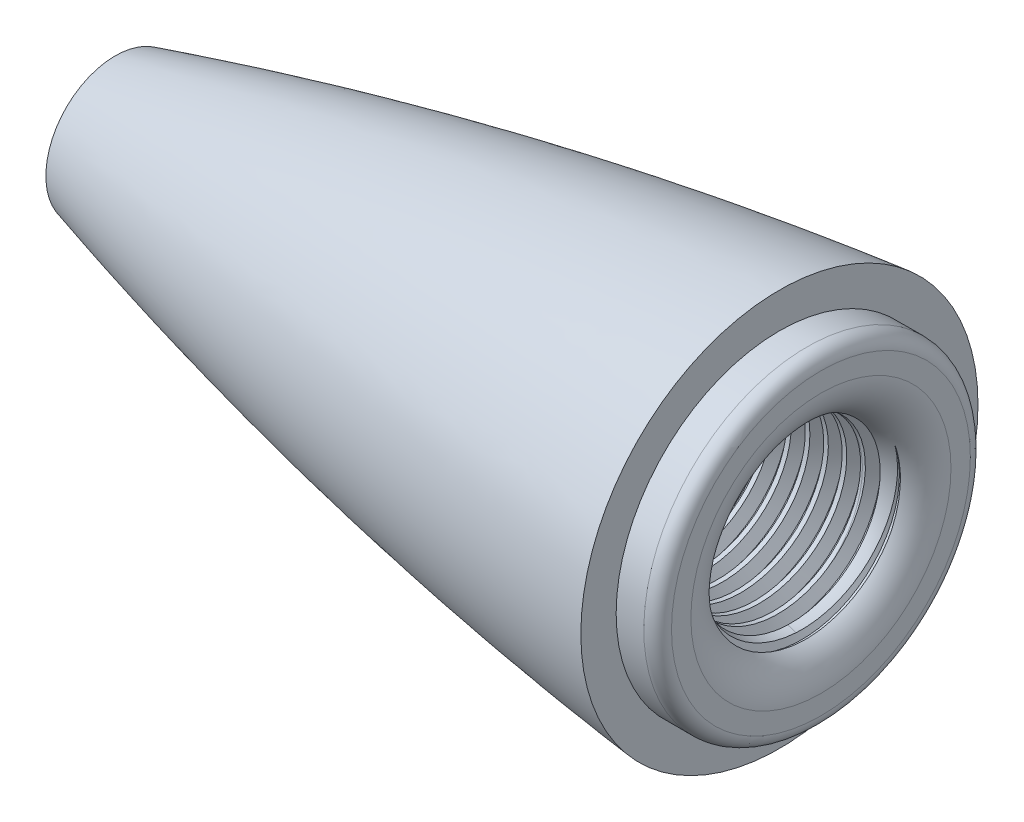
SolidWorks part; units mm, degrees
material "PVC Rigid"
ref_plane "Front Plane" through (0, 0, 0) normal (0, 0, 1) x (1, 0, 0)
ref_plane "Top Plane" through (0, 0, 0) normal (0, 1, 0) x (1, 0, 0)
ref_plane "Right Plane" through (0, 0, 0) normal (1, 0, 0) x (0, 0, -1)
sketch "Sketch1" plane through (0, 0, 0) normal (0, 0, 1) x (1, 0, 0)
  line L8 (304.8, 51.1073) -> (304.8, 42.7482)
  line L9 (25.4, 0.0025) -> (0, 0.0025)
  line L10 (0, 0) -> (-29.9105, 0) construction
  spline S0 degree 9 poles (-29.1265, -10.5907) (11.3631, 4.9002) (51.8527, 17.9688) (92.3423, 28.7808) (132.8319, 37.4498) (173.3216, 44.0564) (213.8112, 48.6546) (254.3008, 51.276) (294.7904, 51.9314) (335.28, 50.6101) knots 0 0 0 0 0 0 0 0 0 0 1 1 1 1 1 1 1 1 1 1 construction
  spline S1 degree 9 poles (0, 0.0025) (33.8667, 11.6877) (67.7333, 21.7382) (101.6, 30.2377) (135.4667, 37.2472) (169.3333, 42.8123) (203.2, 46.965) (237.0667, 49.7266) (270.9333, 51.1073) (304.8, 51.1073) knots 0.079929 0.079929 0.079929 0.079929 0.079929 0.079929 0.079929 0.079929 0.079929 0.079929 0.916357 0.916357 0.916357 0.916357 0.916357 0.916357 0.916357 0.916357 0.916357 0.916357
  spline S2 degree 9 poles (-1.5045, -8.8771) (35.6338, 4.0076) (72.772, 14.9233) (109.9103, 23.9808) (147.0486, 31.2587) (184.1869, 36.8133) (221.3252, 40.6827) (258.4634, 42.8895) (295.6017, 43.4413) (332.74, 42.3304) knots 0 0 0 0 0 0 0 0 0 0 1 1 1 1 1 1 1 1 1 1 construction
  spline S3 degree 9 poles (25.4, 0.0025) (56.4444, 9.7292) (87.4889, 18.1207) (118.5333, 25.2332) (149.5778, 31.1089) (180.6222, 35.7794) (211.6667, 39.2675) (242.7111, 41.588) (273.7556, 42.7482) (304.8, 42.7482) knots 0.080494 0.080494 0.080494 0.080494 0.080494 0.080494 0.080494 0.080494 0.080494 0.080494 0.916409 0.916409 0.916409 0.916409 0.916409 0.916409 0.916409 0.916409 0.916409 0.916409
  dimension "D1" = 25.4
  dimension "D2" = 51.1048
  dimension "D3" = 42.7457
  dimension "D4" = 0.0025
revolve "Revolve1" add sketch "Sketch1" angle 360 about L10
sketch "Sketch6" plane through (0, 0, 0) normal (0, 0, 1) x (1, 0, 0)
  line L0 (0, 0) -> (0, 38.1)
  line L1 (0, 38.1) -> (50.8, 38.1)
  line L2 (50.8, 38.1) -> (50.8, -38.1)
  line L3 (50.8, -38.1) -> (0, -38.1)
  line L4 (0, -38.1) -> (0, 0)
  line L5 (304.8, -42.7482) -> (304.8, 42.7482) construction
  line L6 (304.8, -76.2) -> (203.2, -76.2)
  line L7 (304.8, -76.2) -> (304.8, 76.2)
  line L8 (304.8, 76.2) -> (203.2, 76.2)
  line L9 (203.2, -76.2) -> (203.2, 76.2)
  line L10 (304.8, -76.2) -> (203.2, 76.2) construction
  line L11 (304.8, 76.2) -> (203.2, -76.2) construction
  point P4 (254, 0)
  dimension "D1" = 50.8
  dimension "D2" = 76.2
  dimension "D3" = 203.2
  dimension "D4" = 152.4
extrude "Cut-Extrude1" cut sketch "Sketch6" against normal through all both and the other way through all
sketch "Sketch5" plane through (0, 0, 0) normal (0, 0, 1) x (1, 0, 0)
  line L0 (142.875, 19.685) -> (212.725, 19.685)
  line L1 (212.725, 19.685) -> (212.725, 37.465)
  line L2 (212.725, 37.465) -> (200.66, 37.465)
  line L3 (200.66, 37.465) -> (200.66, 26.035)
  line L4 (200.66, 26.035) -> (152.4, 26.035)
  line L5 (152.4, 26.035) -> (152.4, 32.385)
  line L6 (152.4, 32.385) -> (142.875, 32.385)
  line L7 (142.875, 32.385) -> (142.875, 19.685)
  line L8 (0, 0) -> (304.8, 0) construction
  line L10 (203.2, -45.5679) -> (203.2, 45.5679) construction
  dimension "D1" = 9.525
  dimension "D2" = 19.685
  dimension "D3" = 6.35
  dimension "D4" = 12.065
  dimension "D5" = 9.525
  dimension "D6" = 69.85
  dimension "D7" = 12.7
  dimension "D8" = 37.465
revolve "Revolve2" add sketch "Sketch5" angle 360 about L8
thread "Thread2" pitch 4.2333 start angle 0, offset 3.175, length 0, pitch 4.2333, diameter 39.37
ref_plane "Plane2" through (139.7, 0, -19.685) normal (0, -1, 0) x (0, 0, -1)
sketch "Thread Profile2" plane through (139.7, 0, -19.685) normal (0, -1, 0) x (0, 0, -1)
  line L0 (0, 0) -> (0, 4.2333) construction
  line L1 (0, 0) -> (2.2914, 1.3229)
  line L2 (2.2914, 1.3229) -> (2.2914, 1.8521)
  line L3 (2.2914, 1.8521) -> (0, 3.175)
  line L4 (2.2914, 1.5875) -> (0, 1.5875) construction
  line L11 (0, 0) -> (0, 3.175)
  point P2 (0, 0)
  dimension "Pitch" = 4.2333
  dimension "Profile_Angle" = 60
  dimension "Profile_Land" = 0.5292
  dimension "Profile_Height" = 2.2914
sketch "Sketch7" plane through (0, 0, 0) normal (0, 0, 1) x (1, 0, 0)
  line L4 (50.8, 0) -> (209.7695, 0) construction
  line L5 (50.8, 7.5669) -> (50.8, -7.5669) construction
  line L6 (157.226, 30.48) -> (149.606, 30.48)
  line L7 (149.606, 30.48) -> (149.606, 25.4)
  line L8 (149.606, 25.4) -> (157.226, 25.4)
  line L9 (152.4, -30.2376) -> (152.4, 30.2376) construction
  line L10 (197.485, 36.703) -> (205.105, 36.703)
  line L11 (205.105, 36.703) -> (205.105, 25.908)
  line L12 (205.105, 25.908) -> (197.485, 25.908)
  line L13 (212.725, -37.465) -> (212.725, 37.465) construction
  arc A0 (157.226, 25.4) -> (157.226, 30.48) centre (157.226, 27.94) cw
  arc A1 (197.485, 36.703) -> (197.485, 25.908) centre (194.1399, 31.3055) cw
  dimension "D4" = 2.54
  dimension "D9" = 6.35
  dimension "D1" = 7.62
  dimension "D2" = 5.08
  dimension "D3" = 25.4
  dimension "D5" = 2.794
  dimension "D6" = 7.62
  dimension "D7" = 10.795
  dimension "D8" = 7.62
  dimension "D10" = 25.908
revolve "Revolve4" [suppressed] add sketch "Sketch7" angle 360 about L4
fillet "Fillet1" radius 2.54 1 edges at (142.875, 0, -28.6125)
fillet "Fillet2" radius 1.778 2 edges at (152.4, -26.035, 0) (152.4, 0, -30.2376)
fillet "Fillet3" radius 2.54 2 edges at (200.66, -26.035, 0) (200.66, 0, -36.9274)
sketch "Sketch8" plane through (50.8, 0, 0) normal (-1, 0, 0) x (0, 0, 1)
  circle A0 centre (0, 0) radius 9.525
  dimension "D1" = 19.05
extrude "Cut-Extrude2" cut sketch "Sketch8" against normal up to next
fillet "Fillet4" radius 3.175 1 edges at (212.725, -37.465, 0)
sketch "Sketch10" plane through (0, 0, 0) normal (0, 0, 1) x (1, 0, 0)
  line L0 (202.565, 19.685) -> (212.725, 19.685)
  line L2 (212.725, 19.685) -> (212.725, 29.845)
  line L3 (212.725, -34.29) -> (212.725, 34.29) construction
  line L4 (50.8, 0) -> (212.725, 0) construction
  line L5 (50.8, 15.9261) -> (50.8, -15.9261) construction
  line L6 (202.565, 29.845) -> (212.725, 29.845) construction
  line L7 (202.565, 29.845) -> (202.565, 19.685) construction
  arc A0 (212.725, 29.845) -> (202.565, 19.685) centre (202.565, 29.845) cw
  dimension "D1" = 10.16
  dimension "D2" = 19.685
  dimension "D3" = 90
revolve "Cut-Revolve1" cut sketch "Sketch10" angle 360 about L4
